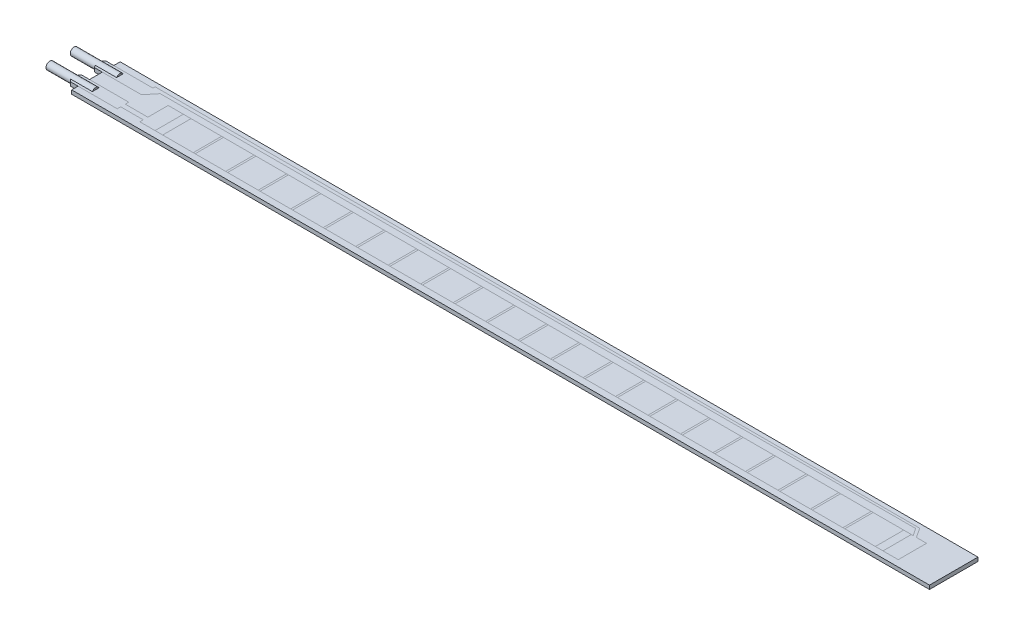
SolidWorks part; units mm, degrees
ref_plane "Front Plane" through (0, 0, 0) normal (0, 0, 1) x (1, 0, 0)
ref_plane "Top Plane" through (0, 0, 0) normal (0, 1, 0) x (1, 0, 0)
ref_plane "Right Plane" through (0, 0, 0) normal (1, 0, 0) x (0, 0, -1)
sketch "Sketch1" plane through (0, 0, 0) normal (0, 1, 0) x (1, 0, 0)
  line L1 (-56.12, -3.175) -> (56.12, -3.175)
  line L2 (-56.12, -3.175) -> (-56.12, 3.175)
  line L3 (-56.12, 3.175) -> (56.12, 3.175)
  line L4 (56.12, -3.175) -> (56.12, 3.175)
  point P0 (0, 0)
  dimension "D1" = 112.24
  dimension "D2" = 6.35
extrude "Boss-Extrude1" add sketch "Sketch1" along normal blind 0.5
sketch "Sketch2" plane through (0, 0.5, 0) normal (0, 1, 0) x (1, 0, 0)
  line L0 (-56.12, 0) -> (-56.12, -3.175) construction
  line L1 (-56.12, 3.175) -> (-56.12, -3.175) construction
  line L2 (-56.12, 0) -> (-56.12, 3.175) construction
  line L3 (-56.12, -2.3375) -> (-50.9922, -2.3375)
  line L4 (-48.0377, -1.2875) -> (-48.0377, 1.3707)
  line L6 (-56.12, -0.8375) -> (-50.9922, -0.8375)
  line L7 (-56.12, 0.8375) -> (-50.9922, 0.8375)
  line L8 (-56.12, 2.3375) -> (-50.9922, 2.3375)
  line L9 (-48.0377, -2.3375) -> (51.1928, -2.3375)
  line L10 (-48.0377, -2.3375) -> (-48.0377, -1.8875)
  line L11 (-48.0377, 1.3707) -> (49.452, 1.3707)
  line L12 (51.1928, -2.3375) -> (51.1928, 1.3707)
  line L13 (-50.9922, 0.8375) -> (-49.8989, 2.1837)
  line L14 (-50.9922, 2.3375) -> (-50.9922, 2.6295)
  line L15 (-50.9922, -1.8875) -> (-48.0377, -1.8875)
  line L16 (-50.9922, -1.2875) -> (-48.0377, -1.2875)
  line L17 (-50.9922, -0.8375) -> (-50.9922, -1.2875)
  line L18 (-50.9922, -2.3375) -> (-50.9922, -1.8875)
  line L19 (-50.9922, 2.6295) -> (49.0295, 2.6295)
  line L21 (49.0295, 2.6295) -> (49.8745, 1.3707)
  line L22 (-49.8989, 2.1837) -> (48.803, 2.3375)
  line L23 (48.803, 2.3375) -> (49.452, 1.3707)
  line L24 (49.8745, 1.3707) -> (51.1928, 1.3707)
  line L26 (-46.0475, -2.3375) -> (49.2025, -2.3375)
  line L27 (-46.0475, -2.3375) -> (-46.0475, 1.3707)
  line L28 (-46.0475, 1.3707) -> (49.2025, 1.3707)
  line L29 (49.2025, -2.3375) -> (49.2025, 1.3707)
  point P26 (1.5775, -0.4834)
  dimension "D3" = 95.25
split line "Split Line1"
sketch "Sketch3" plane through (0, 0.5, 0) normal (0, 1, 0) x (1, 0, 0)
  line L0 (-45.0475, 1.3707) -> (-45.0475, -2.3375)
  line L1 (49.2025, 1.3707) -> (-46.0475, 1.3707) construction
  line L2 (-46.0475, -2.3375) -> (49.2025, -2.3375) construction
  line L3 (48.2025, 1.3707) -> (48.2025, -2.3375)
  line L4 (-46.0475, 1.3707) -> (-46.0475, -2.3375) construction
  line L5 (49.2025, -2.3375) -> (49.2025, 1.3707) construction
  dimension "D1" = 1
  dimension "D2" = 1
split line "Split Line2"
sketch "Sketch4" plane through (0, 0.5, 0) normal (0, 1, 0) x (1, 0, 0)
  line L0 (-45.0475, -2.3375) -> (48.2025, -2.3375) construction
  line L1 (-45.0475, 1.3707) -> (-41.0475, 1.3707)
  line L2 (-45.0475, 1.3707) -> (-45.0475, -2.3375)
  line L3 (-45.0475, -2.3375) -> (-41.0475, -2.3375)
  line L4 (-41.0475, 1.3707) -> (-41.0475, -2.3375)
  line L11 (-40.7975, 1.3707) -> (-36.7975, 1.3707)
  line L12 (-40.7975, 1.3707) -> (-40.7975, -2.3375)
  line L17 (-40.7975, -2.3375) -> (-36.7975, -2.3375)
  line L18 (-36.7975, 1.3707) -> (-36.7975, -2.3375)
  line L29 (-36.5475, 1.3707) -> (-32.5475, 1.3707)
  line L30 (-36.5475, 1.3707) -> (-36.5475, -2.3375)
  line L35 (-36.5475, -2.3375) -> (-32.5475, -2.3375)
  line L36 (-32.5475, 1.3707) -> (-32.5475, -2.3375)
  line L47 (-32.2975, 1.3707) -> (-28.2975, 1.3707)
  line L48 (-32.2975, 1.3707) -> (-32.2975, -2.3375)
  line L53 (-32.2975, -2.3375) -> (-28.2975, -2.3375)
  line L54 (-28.2975, 1.3707) -> (-28.2975, -2.3375)
  line L65 (-28.0475, 1.3707) -> (-24.0475, 1.3707)
  line L66 (-28.0475, 1.3707) -> (-28.0475, -2.3375)
  line L71 (-28.0475, -2.3375) -> (-24.0475, -2.3375)
  line L72 (-24.0475, 1.3707) -> (-24.0475, -2.3375)
  line L83 (-23.7975, 1.3707) -> (-19.7975, 1.3707)
  line L84 (-23.7975, 1.3707) -> (-23.7975, -2.3375)
  line L89 (-23.7975, -2.3375) -> (-19.7975, -2.3375)
  line L90 (-19.7975, 1.3707) -> (-19.7975, -2.3375)
  line L101 (-19.5475, 1.3707) -> (-15.5475, 1.3707)
  line L102 (-19.5475, 1.3707) -> (-19.5475, -2.3375)
  line L107 (-19.5475, -2.3375) -> (-15.5475, -2.3375)
  line L108 (-15.5475, 1.3707) -> (-15.5475, -2.3375)
  line L119 (-15.2975, 1.3707) -> (-11.2975, 1.3707)
  line L120 (-15.2975, 1.3707) -> (-15.2975, -2.3375)
  line L125 (-15.2975, -2.3375) -> (-11.2975, -2.3375)
  line L126 (-11.2975, 1.3707) -> (-11.2975, -2.3375)
  line L133 (-11.0475, 1.3707) -> (-7.0475, 1.3707)
  line L134 (-11.0475, 1.3707) -> (-11.0475, -2.3375)
  line L135 (-11.0475, -2.3375) -> (-7.0475, -2.3375)
  line L136 (-7.0475, 1.3707) -> (-7.0475, -2.3375)
  line L139 (-6.7975, 1.3707) -> (-2.7975, 1.3707)
  line L140 (-6.7975, 1.3707) -> (-6.7975, -2.3375)
  line L141 (-6.7975, -2.3375) -> (-2.7975, -2.3375)
  line L142 (-2.7975, 1.3707) -> (-2.7975, -2.3375)
  line L145 (-2.5475, 1.3707) -> (1.4525, 1.3707)
  line L146 (-2.5475, 1.3707) -> (-2.5475, -2.3375)
  line L147 (-2.5475, -2.3375) -> (1.4525, -2.3375)
  line L148 (1.4525, 1.3707) -> (1.4525, -2.3375)
  line L151 (1.7025, 1.3707) -> (5.7025, 1.3707)
  line L152 (1.7025, 1.3707) -> (1.7025, -2.3375)
  line L153 (1.7025, -2.3375) -> (5.7025, -2.3375)
  line L154 (5.7025, 1.3707) -> (5.7025, -2.3375)
  line L157 (5.9525, 1.3707) -> (9.9525, 1.3707)
  line L158 (5.9525, 1.3707) -> (5.9525, -2.3375)
  line L159 (5.9525, -2.3375) -> (9.9525, -2.3375)
  line L160 (9.9525, 1.3707) -> (9.9525, -2.3375)
  line L163 (10.2025, 1.3707) -> (14.2025, 1.3707)
  line L164 (10.2025, 1.3707) -> (10.2025, -2.3375)
  line L165 (10.2025, -2.3375) -> (14.2025, -2.3375)
  line L166 (14.2025, 1.3707) -> (14.2025, -2.3375)
  line L169 (14.4525, 1.3707) -> (18.4525, 1.3707)
  line L170 (14.4525, 1.3707) -> (14.4525, -2.3375)
  line L171 (14.4525, -2.3375) -> (18.4525, -2.3375)
  line L172 (18.4525, 1.3707) -> (18.4525, -2.3375)
  line L175 (18.7025, 1.3707) -> (22.7025, 1.3707)
  line L176 (18.7025, 1.3707) -> (18.7025, -2.3375)
  line L177 (18.7025, -2.3375) -> (22.7025, -2.3375)
  line L178 (22.7025, 1.3707) -> (22.7025, -2.3375)
  line L181 (22.9525, 1.3707) -> (26.9525, 1.3707)
  line L182 (22.9525, 1.3707) -> (22.9525, -2.3375)
  line L183 (22.9525, -2.3375) -> (26.9525, -2.3375)
  line L184 (26.9525, 1.3707) -> (26.9525, -2.3375)
  line L187 (27.2025, 1.3707) -> (31.2025, 1.3707)
  line L188 (27.2025, 1.3707) -> (27.2025, -2.3375)
  line L189 (27.2025, -2.3375) -> (31.2025, -2.3375)
  line L190 (31.2025, 1.3707) -> (31.2025, -2.3375)
  line L193 (31.4525, 1.3707) -> (35.4525, 1.3707)
  line L194 (31.4525, 1.3707) -> (31.4525, -2.3375)
  line L195 (31.4525, -2.3375) -> (35.4525, -2.3375)
  line L196 (35.4525, 1.3707) -> (35.4525, -2.3375)
  line L199 (35.7025, 1.3707) -> (39.7025, 1.3707)
  line L200 (35.7025, 1.3707) -> (35.7025, -2.3375)
  line L201 (35.7025, -2.3375) -> (39.7025, -2.3375)
  line L202 (39.7025, 1.3707) -> (39.7025, -2.3375)
  line L205 (39.9525, 1.3707) -> (43.9525, 1.3707)
  line L206 (39.9525, 1.3707) -> (39.9525, -2.3375)
  line L207 (39.9525, -2.3375) -> (43.9525, -2.3375)
  line L208 (43.9525, 1.3707) -> (43.9525, -2.3375)
  line L211 (44.2025, 1.3707) -> (48.2025, 1.3707)
  line L212 (44.2025, 1.3707) -> (44.2025, -2.3375)
  line L213 (44.2025, -2.3375) -> (48.2025, -2.3375)
  line L214 (48.2025, 1.3707) -> (48.2025, -2.3375)
  point P4 (-43.0475, -0.4834)
  point P14 (-38.7975, -0.4834)
  point P19 (-34.5475, -0.4834)
  point P24 (-30.2975, -0.4834)
  point P29 (-26.0475, -0.4834)
  point P34 (-21.7975, -0.4834)
  point P39 (-17.5475, -0.4834)
  point P44 (-13.2975, -0.4834)
  point P49 (-9.0475, -0.4834)
  point P54 (-4.7975, -0.4834)
  point P59 (-0.5475, -0.4834)
  point P64 (3.7025, -0.4834)
  point P69 (7.9525, -0.4834)
  point P74 (12.2025, -0.4834)
  point P79 (16.4525, -0.4834)
  point P84 (20.7025, -0.4834)
  point P89 (24.9525, -0.4834)
  point P94 (29.2025, -0.4834)
  point P99 (33.4525, -0.4834)
  point P104 (37.7025, -0.4834)
  point P109 (41.9525, -0.4834)
  point P114 (46.2025, -0.4834)
  dimension "D2" = 4
  dimension "D1" = 22
split line "Split Line3"
sketch "Sketch5" plane through (0, 0.5, 0) normal (0, 1, 0) x (1, 0, 0)
  line L0 (-56.12, -2.3375) -> (-57.1332, -2.3375)
  line L1 (-57.1332, -2.3375) -> (-57.5631, -1.822)
  line L5 (-56.12, -0.8375) -> (-56.12, -2.3375)
  line L6 (-57.1332, -0.8375) -> (-57.5631, -1.353)
  line L7 (-56.12, -0.8375) -> (-57.1332, -0.8375)
  line L8 (-57.5631, -1.353) -> (-57.5631, -1.822)
  line L9 (-56.12, 0) -> (-58.8012, 0) construction
  line L10 (-56.12, 0.8375) -> (-56.12, -0.8375) construction
  line L11 (-57.5631, 1.353) -> (-57.5631, 1.822)
  line L12 (-56.12, 0.8375) -> (-57.1332, 0.8375)
  line L13 (-57.1332, 0.8375) -> (-57.5631, 1.353)
  line L14 (-56.12, 0.8375) -> (-56.12, 2.3375)
  line L15 (-57.1332, 2.3375) -> (-57.5631, 1.822)
  line L16 (-56.12, 2.3375) -> (-57.1332, 2.3375)
extrude "Boss-Extrude2" add sketch "Sketch5" against normal blind 0.5
sketch "Sketch6" plane through (-57.5631, 0, 0) normal (-1, 0, 0) x (0, 0, 1)
  line L3 (0, 0) -> (0, 0.3953) construction
  circle A0 centre (1.5875, 0.25) radius 0.5
  circle A1 centre (-1.5875, 0.25) radius 0.5
  dimension "D1" = 1
extrude "Boss-Extrude3" add sketch "Sketch6" along normal blind 3 and the other way blind 3
